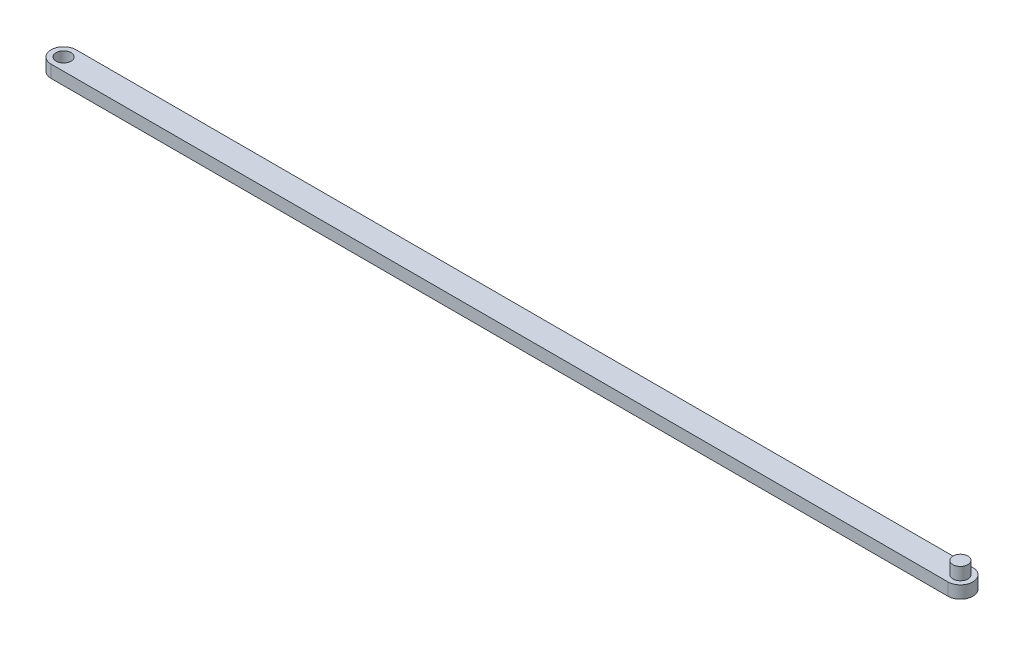
SolidWorks part; units mm, degrees
ref_plane "前视基准面" through (0, 0, 0) normal (0, 0, 1) x (1, 0, 0)
ref_plane "上视基准面" through (0, 0, 0) normal (0, 1, 0) x (1, 0, 0)
ref_plane "右视基准面" through (0, 0, 0) normal (1, 0, 0) x (0, 0, -1)
sketch "草图1" plane through (0, 0, 0) normal (0, 1, 0) x (1, 0, 0)
  line L0 (0, 0) -> (359.9, 0)
  line L2 (359.9, -10) -> (0, -10)
  arc A0 (0, 0) -> (0, -10) centre (0, -5) ccw
  arc A1 (359.9, -10) -> (359.9, 0) centre (359.9, -5) ccw
  circle A2 centre (0, -5) radius 3
  dimension "D1" = 359.9
  dimension "D2" = 5
extrude "凸台-拉伸1" add sketch "草图1" along normal blind 5
sketch "草图2" plane through (0, 5, 0) normal (0, 1, 0) x (1, 0, 0)
  circle A0 centre (359.9, -5) radius 3
extrude "凸台-拉伸2" add sketch "草图2" along normal blind 5
